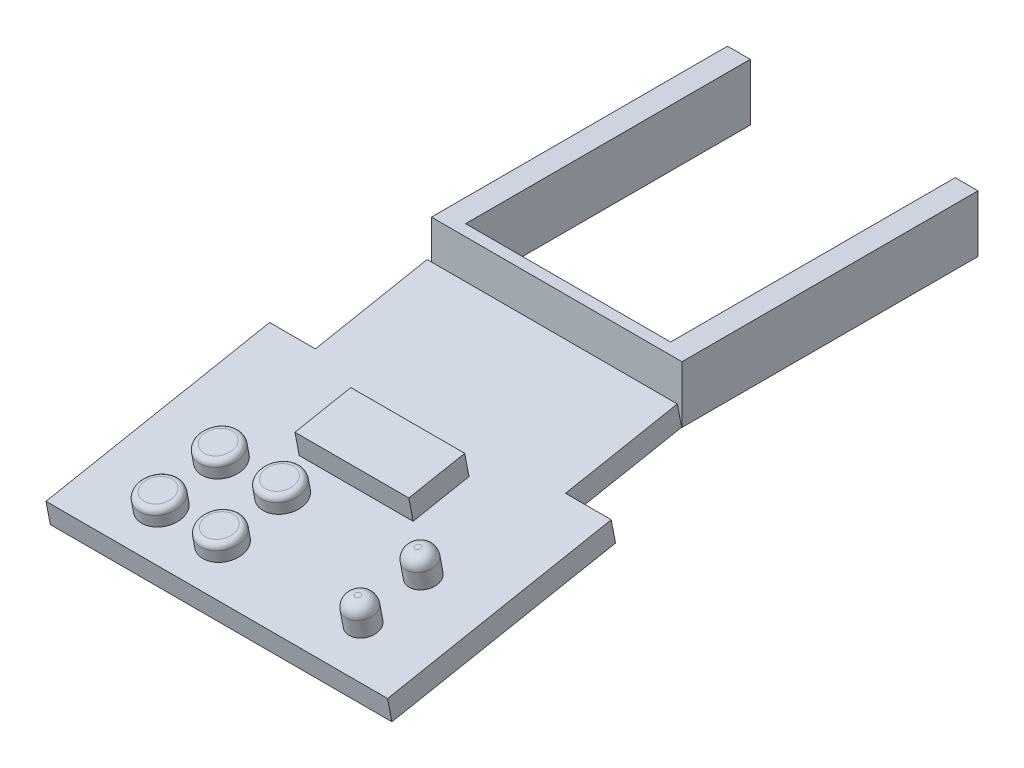
SolidWorks part; units mm, degrees
ref_plane "Front Plane" through (0, 0, 0) normal (0, 0, 1) x (1, 0, 0)
ref_plane "Top Plane" through (0, 0, 0) normal (0, 1, 0) x (1, 0, 0)
ref_plane "Right Plane" through (0, 0, 0) normal (1, 0, 0) x (0, 0, -1)
sketch "Sketch1" plane through (0, 0, 0) normal (0, 1, 0) x (1, 0, 0)
  line L0 (18, 23.2222) -> (22, 23.2222)
  line L1 (-22, 23.2222) -> (-18, 23.2222)
  line L2 (-22, 23.2222) -> (-22, -26.7778)
  line L3 (-22, -26.7778) -> (-18, -26.7778)
  line L4 (-18, 23.2222) -> (-18, -26.7778)
  line L5 (18, 23.2222) -> (18, -26.7778)
  line L6 (18, -26.7778) -> (22, -26.7778)
  line L7 (22, 23.2222) -> (22, -26.7778)
  dimension "D1" = 4
  dimension "D2" = 50
  dimension "D3" = 4
  dimension "D4" = 50
  dimension "D5" = 44
extrude "Boss-Extrude1" add sketch "Sketch1" along normal blind 10
sketch "Sketch2" plane through (0, 0, 26.7778) normal (0, 0, 1) x (1, 0, 0)
  line L1 (-22, 10) -> (22, 10)
  line L2 (-22, 10) -> (-22, 0)
  line L3 (-22, 0) -> (22, 0)
  line L4 (22, 10) -> (22, 0)
extrude "Boss-Extrude2" add sketch "Sketch2" along normal blind 2
ref_plane "Plane1" through (0, 5.3368, 1.0263) normal (0, 0.982, 0.1888) x (1, 0, 0)
sketch "Sketch3" plane through (0, 5.3368, 1.0263) normal (0, 0.982, 0.1888) x (1, 0, 0)
  line L1 (-22, -28.26) -> (21.9437, -28.26)
  line L2 (-22, -28.26) -> (-22, -48.26)
  line L3 (-22, -48.26) -> (21.9437, -48.26)
  line L4 (21.9437, -28.26) -> (21.9437, -48.26)
  line L5 (-30.0281, -48.26) -> (29.9719, -48.26)
  line L6 (-30.0281, -48.26) -> (-30.0281, -88.26)
  line L7 (-30.0281, -88.26) -> (29.9719, -88.26)
  line L8 (29.9719, -48.26) -> (29.9719, -88.26)
  point P9 (-0.0281, -48.26)
  dimension "D1" = 20
  dimension "D2" = 40
  dimension "D3" = 60
  dimension "D4" = 30
extrude "Boss-Extrude3" add sketch "Sketch3" along normal blind 4 separate body contours L4 L1 L2 L3 | L8 L5 L3 L6 L7 region at (-0.0281, -1.8885, 38.5978) region at (-0.0281, -7.5539, 68.058)
sketch "Sketch4" plane through (0, 9.2648, 1.7817) normal (0, 0.982, 0.1888) x (1, 0, 0)
  line L0 (-30.0281, -48.26) -> (-30.0281, -88.26) construction
  line L1 (-10.0281, -53.3275) -> (9.9719, -53.3275)
  line L2 (-10.0281, -53.3275) -> (-10.0281, -63.3275)
  line L3 (-10.0281, -63.3275) -> (9.9719, -63.3275)
  line L4 (9.9719, -53.3275) -> (9.9719, -63.3275)
  circle A0 centre (-17.4526, -69.6913) radius 3.5
  circle A1 centre (-17.4526, -80.449) radius 3.5
  circle A2 centre (-6.6949, -69.6913) radius 3.5
  circle A3 centre (-6.6949, -80.449) radius 3.5
  circle A4 centre (18.0024, -69.6913) radius 2.5
  circle A5 centre (18.0024, -80.449) radius 2.5
  point P4 (-0.0281, -63.3275)
  dimension "D4" = 7
  dimension "D5" = 7
  dimension "D6" = 7
  dimension "D7" = 7
  dimension "D8" = 5
  dimension "D9" = 5
  dimension "D1" = 20
  dimension "D2" = 10
  dimension "D3" = 30
extrude "Boss-Extrude4" add sketch "Sketch4" along normal blind 4 contours L1 L4 L3 L2
extrude "Boss-Extrude5" add sketch "Sketch4<3>" along normal blind 3 contours A2
sketch "Sketch4<3>" plane through (0, 9.2648, 1.7817) normal (0, 0.982, 0.1888) x (1, 0, 0) same geometry as "Sketch4"
extrude "Boss-Extrude6" add sketch "Sketch4<4>" along normal blind 3 contours A0 | A1 | A3
sketch "Sketch4<4>" plane through (0, 9.2648, 1.7817) normal (0, 0.982, 0.1888) x (1, 0, 0) same geometry as "Sketch4"
extrude "Boss-Extrude7" add sketch "Sketch4<5>" along normal blind 5 contours A5 | A4
sketch "Sketch4<5>" plane through (0, 9.2648, 1.7817) normal (0, 0.982, 0.1888) x (1, 0, 0) same geometry as "Sketch4"
fillet "Fillet1" radius 2 2 edges at (18.0024, -1.4898, 84.1824) (18.0024, 0.5417, 73.6183)
fillet "Fillet2" radius 1 4 edges at (-17.4526, -3.6427, 84.7867) (-6.6949, -3.6427, 84.7867) (-6.6949, -1.6111, 74.2226) (-17.4526, -1.6111, 74.2226)
